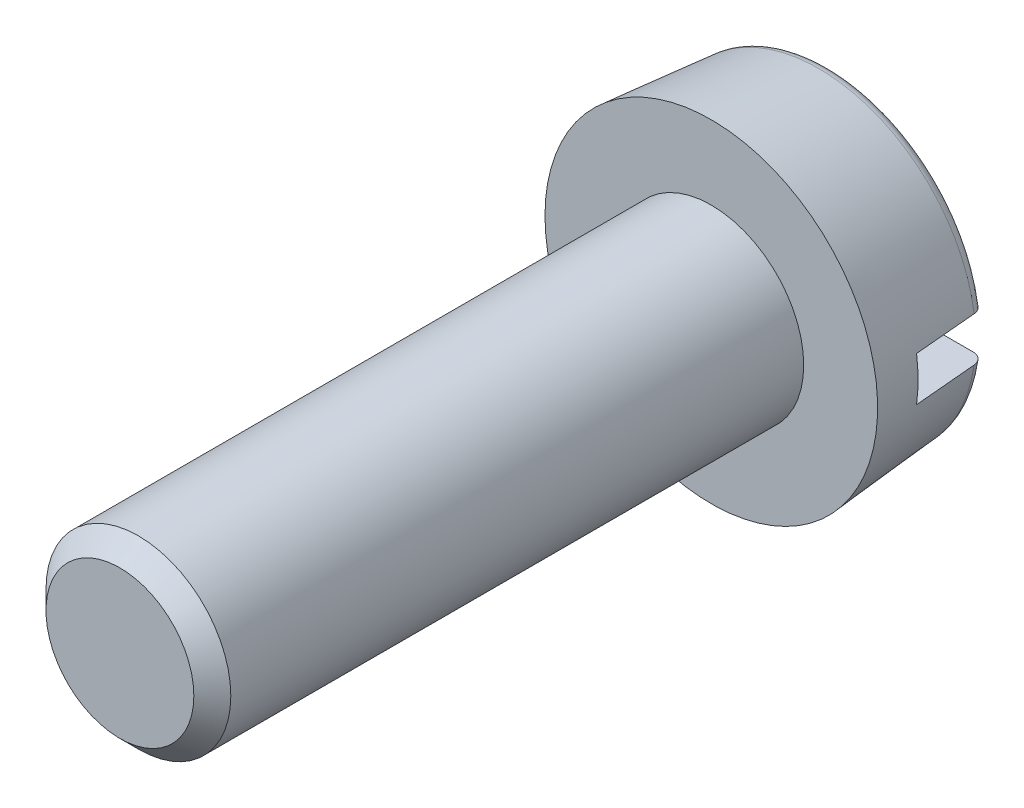
SolidWorks part; units mm, degrees
note: '?' marks a value the reader was unsure of.
ref_plane "Plan1" through (0, 0, 0) normal (0, 0, 1) x (1, 0, 0)
ref_plane "Plan2" through (0, 0, 0) normal (0, 1, 0) x (1, 0, 0)
ref_plane "Plan3" through (0, 0, 0) normal (1, 0, 0) x (0, 0, -1)
ref_axis "Z Axis" through (0, 0, -50) along (0, 0, 1)?
sketch "Esquisse1" plane through (0, 0, 0) normal (0, 1, 0) x (1, 0, 0)
  line L0 (0, 0) -> (0, 1.6) construction
  line L1 (0, 0) -> (2.25, 0)
  line L2 (0, 0) -> (0, 1.6)
  line L3 (0, 1.6) -> (1.9634, 1.6)
  line L5 (2.25, 0) -> (2.1228, 1.4539)
  arc A0 (1.9634, 1.6) -> (2.1228, 1.4539) centre (1.9634, 1.44) cw
  dimension "D3" = 0.16
  dimension "D1" = 2.25
  dimension "D2" = 1.6
  dimension "D4" = 5
revolve "Base-Révolution" add sketch "Esquisse1" angle 360 about L0
sketch "Esquisse2" plane through (0, 0, -1.6) normal (0, 0, 1) x (1, 0, 0)
  line L1 (-2.25, 0.3) -> (2.25, 0.3)
  line L2 (-2.25, 0.3) -> (-2.25, -0.3)
  line L3 (-2.25, -0.3) -> (2.25, -0.3)
  line L4 (2.25, 0.3) -> (2.25, -0.3)
  circle A0 centre (0, 0) radius 2.25 construction
  dimension "D1" = 0.3
extrude "Enlev. mat.-Extru.1" cut sketch "Esquisse2" along normal blind 1
sketch "Esquisse3" plane through (0, 0, 0) normal (0, 1, 0) x (1, 0, 0)
  line L1 (0, 0) -> (0, -8) construction
  line L2 (0, 0) -> (1.25, 0)
  line L3 (0, 0) -> (0, -8)
  line L4 (0, -8) -> (1.25, -8)
  line L6 (1.25, 0) -> (1.25, -8)
  dimension "D1" = 8
  dimension "D2" = 1.25
revolve "Boss.-Révol.1" add sketch "Esquisse3"
cosmetic thread "Représentation de filetage1"
chamfer "Chanfrein1" distance 0.25 angle 45
